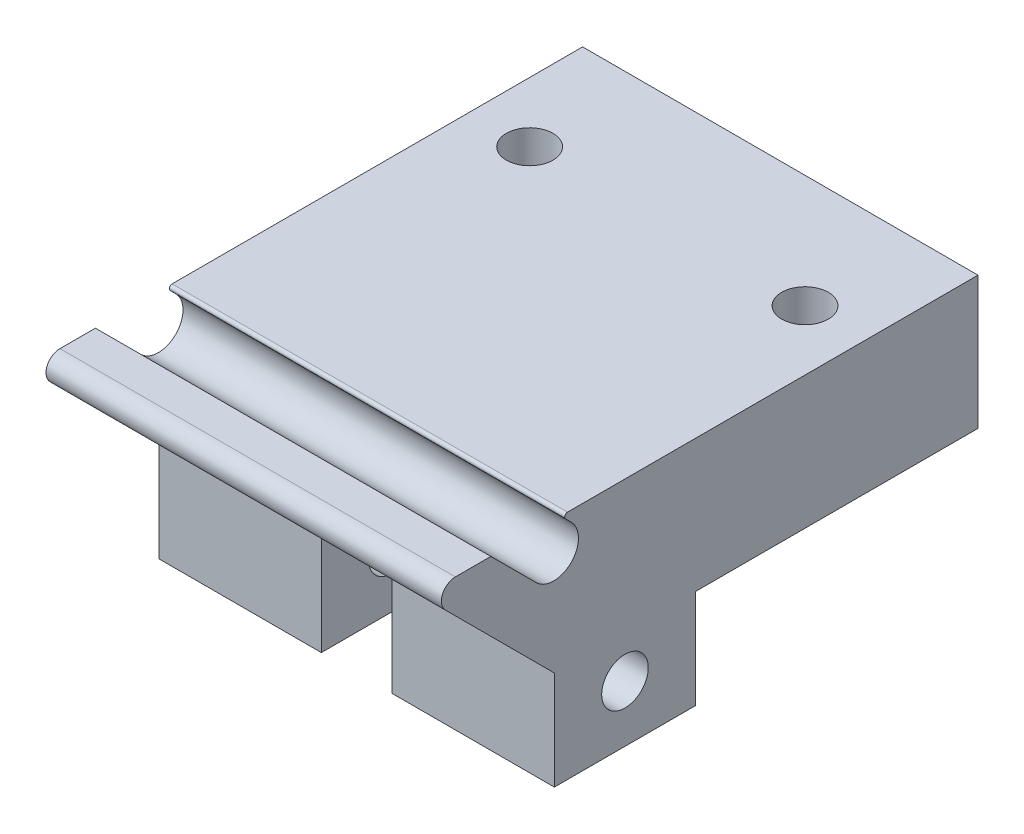
SolidWorks part; units mm, degrees
ref_plane "Front Plane" through (0, 0, 0) normal (0, 0, 1) x (1, 0, 0)
ref_plane "Top Plane" through (0, 0, 0) normal (0, 1, 0) x (1, 0, 0)
ref_plane "Right Plane" through (0, 0, 0) normal (1, 0, 0) x (0, 0, -1)
sketch "Sketch2" plane through (0, 0, 0) normal (0, 0, 1) x (1, 0, 0)
  line L1 (14, 4.699) -> (-14, 4.699)
  line L2 (14, 4.699) -> (14, -4.699)
  line L3 (14, -4.699) -> (-14, -4.699)
  line L4 (-14, 4.699) -> (-14, -4.699)
  line L5 (14, 4.699) -> (-14, -4.699) construction
  line L6 (14, -4.699) -> (-14, 4.699) construction
  point P0 (0, 0)
  dimension "D1" = 9.398
  dimension "D2" = 28
extrude "Boss-Extrude1" add sketch "Sketch2" along normal blind 30
sketch "Sketch3" plane through (14, 0, 0) normal (1, 0, 0) x (0, 0, -1)
  line L0 (-30, 0) -> (0, 0) construction
  circle A0 centre (-30, 0) radius 7.5
  dimension "D1" = 15
  dimension "D2" = 30
extrude "Cut-Extrude1" [suppressed] cut sketch "Sketch3" against normal blind 45
sketch "Sketch5" plane through (0, -4.699, 0) normal (0, -1, 0) x (1, 0, 0)
  line L0 (0, 19.5) -> (0, 0) construction
  line L5 (-2, 19.5) -> (2, 19.5)
  line L6 (-2, 19.5) -> (-2, 21)
  line L7 (-2, 21) -> (2, 21)
  line L8 (2, 19.5) -> (2, 21)
  line L15 (-2, 19.5) -> (-15, 19.5) construction
  line L16 (2, 19.5) -> (15, 19.5) construction
  line L27 (-14, 0) -> (14, 0) construction
  dimension "D1" = 4
  dimension "D2" = 1.5
  dimension "D4" = 21
extrude "Cut-Extrude3" [suppressed] cut sketch "Sketch5" against normal blind 39
fillet "Fillet1" [suppressed] radius 9
hole_wizard "M4x0.7 Tapped Hole1" positions "Sketch7" profile "Sketch6" tap size "M4x0.7" standard "ANSI Metric" end condition through all
sketch "Sketch7" plane through (0, -4.699, 0) normal (0, -1, 0) x (-1, 0, 0)
  line L0 (0, 0) -> (0, -8) construction
  line L3 (9.75, -8) -> (-9.75, -8) construction
  point P0 (-9.75, -8)
  point P2 (9.75, -8)
  dimension "D1" = 19.5
  dimension "D2" = 8
cosmetic thread "Hole Thread1" parameters "D2"=4
cosmetic thread "Hole Thread2" parameters "D2"=4
sketch "Sketch6" plane through (9.75, -4.699, 8) normal (1, 0, 0) x (0, 0, -1)
  line L0 (0, 0) -> (0, 9.398)
  line L1 (0, 9.398) -> (1.65, 9.398)
  line L2 (1.65, 9.398) -> (1.65, 0)
  line L5 (1.65, 0) -> (0, 0)
  line L11 (0, -6.35) -> (0, 107.95) construction
  dimension "Thru Tap Drill Dia." = 3.3
  dimension "Thru Tap Drill Depth" = 9.398
sketch "Sketch8" plane through (0, -4.699, 0) normal (0, -1, 0) x (1, 0, 0)
  line L0 (-14, 30) -> (14, 30) construction
  line L1 (-14, 20) -> (-2.5, 20)
  line L2 (-14, 20) -> (-14, 30)
  line L3 (-14, 30) -> (-2.5, 30)
  line L4 (-2.5, 20) -> (-2.5, 30)
  line L5 (2.5, 20) -> (14, 20)
  line L6 (2.5, 20) -> (2.5, 30)
  line L7 (2.5, 30) -> (14, 30)
  line L8 (14, 20) -> (14, 30)
  dimension "D1" = 11.5
  dimension "D2" = 10
extrude "Boss-Extrude2" add sketch "Sketch8" along normal blind 7
hole_wizard "M4x0.7 Tapped Hole2" positions "Sketch17" profile "Sketch18" tap size "M4x0.7" standard "ANSI Metric" end condition through all
sketch "Sketch17" plane through (-14, 0, 0) normal (-1, 0, 0) x (0, 0, 1)
  line L0 (20, -4.699) -> (0, -4.699) construction
  line L1 (25, -7.699) -> (25, -11.699) construction
  line L2 (30, -11.699) -> (20, -11.699) construction
  point P0 (25, -7.699)
  dimension "D1" = 3
sketch "Sketch18" plane through (-14, -7.699, 25) normal (0, 1, 0) x (0, 0, 1)
  line L0 (0, 0) -> (0, 28)
  line L1 (0, 28) -> (1.65, 28)
  line L2 (1.65, 28) -> (1.65, 0)
  line L5 (1.65, 0) -> (0, 0)
  line L11 (0, -6.35) -> (0, 107.95) construction
  dimension "Thru Tap Drill Dia." = 3.3
  dimension "Thru Tap Drill Depth" = 28
cosmetic thread "Hole Thread3" parameters "D2"=4
sketch "Sketch16" plane through (0, 0, 30) normal (0, 0, 1) x (1, 0, 0)
  line L4 (-14, 4.699) -> (-14, -4.699)
  line L5 (14, 4.699) -> (-14, 4.699)
  line L6 (14, -4.699) -> (14, 4.699)
  line L7 (-14, -4.699) -> (14, -4.699)
  line L8 (-14, 4.699) -> (-14, -4.699)
  line L9 (14, 4.699) -> (-14, 4.699)
  line L10 (14, -4.699) -> (14, 4.699)
  line L11 (-14, -4.699) -> (14, -4.699)
  dimension "D1" = 0
extrude "Boss-Extrude3" add sketch "Sketch16" along normal blind 8
sketch "Sketch15" plane through (-14, 0, 0) normal (-1, 0, 0) x (0, 0, 1)
  line L1 (34.5, 4.699) -> (30.0452, 0.2442)
  line L2 (38, 4.699) -> (0, 4.699) construction
  line L3 (30.0452, 0.2442) -> (27.5704, 2.7191)
  line L4 (27.5704, 2.7191) -> (29.5503, 4.699)
  line L5 (29.5503, 4.699) -> (34.5, 4.699)
  line L7 (0, 4.699) -> (0, -4.699) construction
  dimension "D1" = 3.5
  dimension "D2" = 45
  dimension "D3" = 34.5
  dimension "D4" = 6.3
extrude "Cut-Extrude7" cut sketch "Sketch15" against normal through all
fillet "Fillet2" 2 edges at (0, 2.7191, 27.5704) (0, 0.2442, 30.0452) type full round first side face at (0, 3.7091, 28.5603) second side face at (0, 2.4716, 32.2726) middle face at (0, 1.4817, 28.8078)
fillet "Fillet3" radius 0.2 1 edges at (0, 4.699, 29.5503)
chamfer "Chamfer1" distance 8 angle 45 1 edges at (0, -4.699, 38)
fillet "Fillet4" 2 edges at (0, 4.699, 38) (0, 3.301, 38) type full round first side face at (0, 4.699, 36.25) second side face at (-1.5, -2.0323, 32.6667) middle face at (0, 4, 38)
